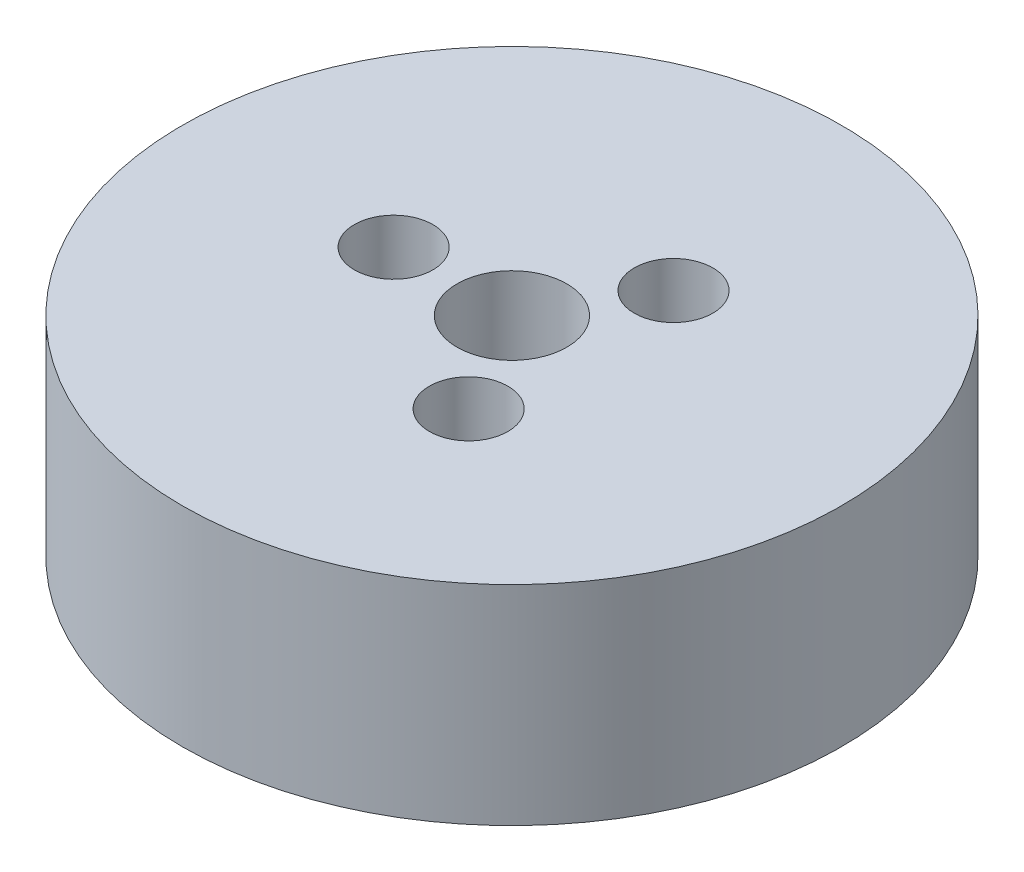
SolidWorks part; units mm, degrees
ref_plane "Front Plane" through (0, 0, 0) normal (0, 0, 1) x (1, 0, 0)
ref_plane "Top Plane" through (0, 0, 0) normal (0, 1, 0) x (1, 0, 0)
ref_plane "Right Plane" through (0, 0, 0) normal (1, 0, 0) x (0, 0, -1)
sketch "Sketch1" plane through (0, 0, 0) normal (0, 1, 0) x (1, 0, 0)
  circle A0 centre (0, 0) radius 30
  dimension "FLANGE_OD" = 60
extrude "Boss-Extrude1" add sketch "Sketch1" along normal blind 19
sketch "Sketch2" plane through (0, 0, 0) normal (0, 1, 0) x (1, 0, 0)
  circle A0 centre (0, 0) radius 5
  dimension "BORE_D" = 10
extrude "Cut-Extrude1" cut sketch "Sketch2" along normal through all
sketch "Sketch3" plane through (0, 19, 0) normal (0, 1, 0) x (1, 0, 0)
  circle A0 centre (0, 0) radius 10.7693 construction
  circle A1 centre (-10.7693, 0) radius 3.5764
  dimension "BOLT_D" = 7.1528
  dimension "BOLT_PCD" = 21.5387
extrude "Cut-Extrude2" cut sketch "Sketch3" against normal blind 16.6072
pattern_circular "CirPattern1" count 3 over 360 about axis through (0, 0, 0) along (0, 1, 0) of "Cut-Extrude2"
